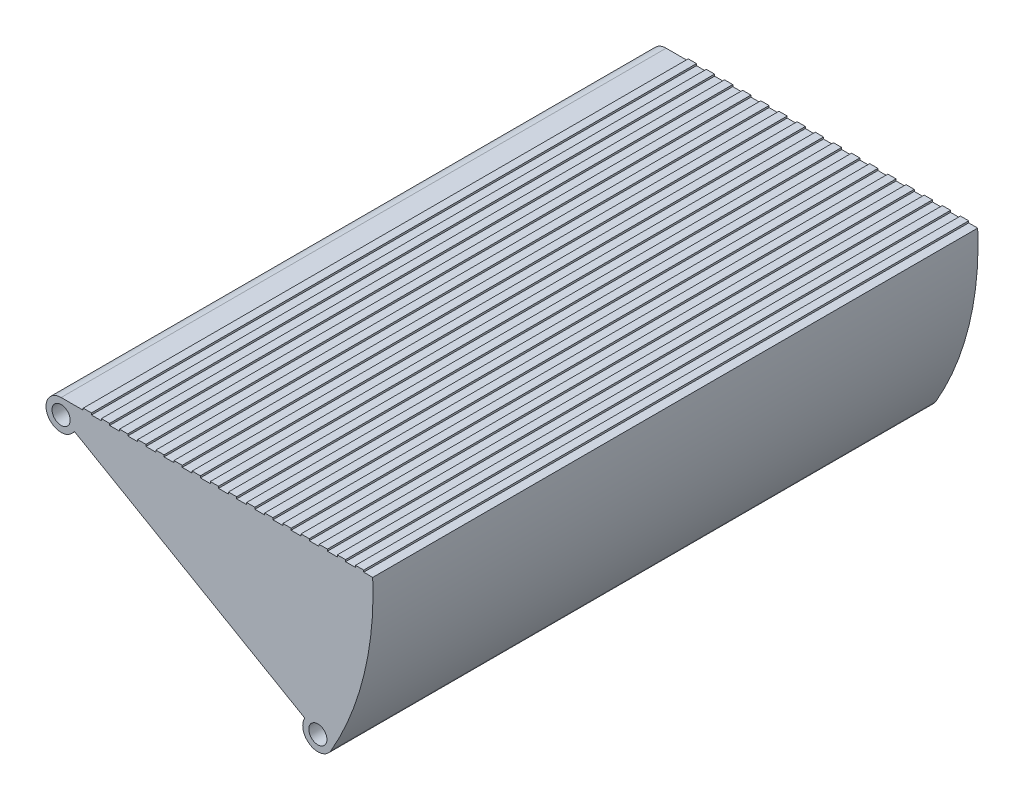
SolidWorks part; units mm, degrees
ref_plane "Front" through (0, 0, 0) normal (0, 0, 1) x (1, 0, 0)
ref_plane "Top" through (0, 0, 0) normal (0, 1, 0) x (1, 0, 0)
ref_plane "Right" through (0, 0, 0) normal (1, 0, 0) x (0, 0, -1)
sketch "Sketch1" plane through (0, 0, 0) normal (0, 0, 1) x (1, 0, 0)
  line L0 (90.6476, 270) -> (-424.3524, 270)
  line L1 (-402.7018, 232.5) -> (-21.6506, 12.5)
  circle A0 centre (-424.3524, 245) radius 15
  arc A1 (-21.6506, 12.5) -> (21.6506, -12.5) centre (0, 0) ccw
  arc A2 (21.6506, -12.5) -> (90.6476, 270) centre (-427.6732, 246.9173) ccw
  arc A3 (-424.3524, 270) -> (-402.7018, 232.5) centre (-424.3524, 245) ccw
  circle A4 centre (0, 0) radius 15
extrude "Boss-Extrude1" add sketch "Sketch1" along normal blind 1000
sketch "Sketch2" plane through (0, 0, 1000) normal (0, 0, 1) x (1, 0, 0)
  line L0 (90.6476, 270) -> (-424.3524, 270) construction
  line L1 (-387.8242, 270) -> (-374.2178, 270)
  line L2 (-387.8242, 270) -> (-387.8242, 273.0178)
  line L3 (-387.8242, 273.0178) -> (-374.2178, 273.0178)
  line L4 (-374.2178, 270) -> (-374.2178, 273.0178)
  line L5 (-357.8242, 270) -> (-357.8242, 273.0178)
  line L6 (-357.8242, 270) -> (-344.2178, 270)
  line L7 (-344.2178, 270) -> (-344.2178, 273.0178)
  line L8 (-357.8242, 273.0178) -> (-344.2178, 273.0178)
  line L9 (-327.8242, 270) -> (-327.8242, 273.0178)
  line L10 (-327.8242, 270) -> (-314.2178, 270)
  line L11 (-314.2178, 270) -> (-314.2178, 273.0178)
  line L12 (-327.8242, 273.0178) -> (-314.2178, 273.0178)
  line L13 (-297.8242, 270) -> (-297.8242, 273.0178)
  line L14 (-297.8242, 270) -> (-284.2178, 270)
  line L15 (-284.2178, 270) -> (-284.2178, 273.0178)
  line L16 (-297.8242, 273.0178) -> (-284.2178, 273.0178)
  line L17 (-267.8242, 270) -> (-267.8242, 273.0178)
  line L18 (-267.8242, 270) -> (-254.2178, 270)
  line L19 (-254.2178, 270) -> (-254.2178, 273.0178)
  line L20 (-267.8242, 273.0178) -> (-254.2178, 273.0178)
  line L21 (-237.8242, 270) -> (-237.8242, 273.0178)
  line L22 (-237.8242, 270) -> (-224.2178, 270)
  line L23 (-224.2178, 270) -> (-224.2178, 273.0178)
  line L24 (-237.8242, 273.0178) -> (-224.2178, 273.0178)
  line L25 (-207.8242, 270) -> (-207.8242, 273.0178)
  line L26 (-207.8242, 270) -> (-194.2178, 270)
  line L27 (-194.2178, 270) -> (-194.2178, 273.0178)
  line L28 (-207.8242, 273.0178) -> (-194.2178, 273.0178)
  line L29 (-177.8242, 270) -> (-177.8242, 273.0178)
  line L30 (-177.8242, 270) -> (-164.2178, 270)
  line L31 (-164.2178, 270) -> (-164.2178, 273.0178)
  line L32 (-177.8242, 273.0178) -> (-164.2178, 273.0178)
  line L33 (-147.8242, 270) -> (-147.8242, 273.0178)
  line L34 (-147.8242, 270) -> (-134.2178, 270)
  line L35 (-134.2178, 270) -> (-134.2178, 273.0178)
  line L36 (-147.8242, 273.0178) -> (-134.2178, 273.0178)
  line L37 (-117.8242, 270) -> (-117.8242, 273.0178)
  line L38 (-117.8242, 270) -> (-104.2178, 270)
  line L39 (-104.2178, 270) -> (-104.2178, 273.0178)
  line L40 (-117.8242, 273.0178) -> (-104.2178, 273.0178)
  line L41 (-87.8242, 270) -> (-87.8242, 273.0178)
  line L42 (-87.8242, 270) -> (-74.2178, 270)
  line L43 (-74.2178, 270) -> (-74.2178, 273.0178)
  line L44 (-87.8242, 273.0178) -> (-74.2178, 273.0178)
  line L45 (-57.8242, 270) -> (-57.8242, 273.0178)
  line L46 (-57.8242, 270) -> (-44.2178, 270)
  line L47 (-44.2178, 270) -> (-44.2178, 273.0178)
  line L48 (-57.8242, 273.0178) -> (-44.2178, 273.0178)
  line L49 (-27.8242, 270) -> (-27.8242, 273.0178)
  line L50 (-27.8242, 270) -> (-14.2178, 270)
  line L51 (-14.2178, 270) -> (-14.2178, 273.0178)
  line L52 (-27.8242, 273.0178) -> (-14.2178, 273.0178)
  line L53 (2.1758, 270) -> (2.1758, 273.0178)
  line L54 (2.1758, 270) -> (15.7822, 270)
  line L55 (15.7822, 270) -> (15.7822, 273.0178)
  line L56 (2.1758, 273.0178) -> (15.7822, 273.0178)
  line L57 (32.1758, 270) -> (32.1758, 273.0178)
  line L58 (32.1758, 270) -> (45.7822, 270)
  line L59 (45.7822, 270) -> (45.7822, 273.0178)
  line L60 (32.1758, 273.0178) -> (45.7822, 273.0178)
  line L61 (62.1758, 270) -> (62.1758, 273.0178)
  line L62 (62.1758, 270) -> (75.7822, 270)
  line L63 (75.7822, 270) -> (75.7822, 273.0178)
  line L64 (62.1758, 273.0178) -> (75.7822, 273.0178)
  dimension "D1" = 16
extrude "Boss-Extrude2" add sketch "Sketch2" against normal up to surface (1000 mm away) up to face at (-152.2371, 145.4333, 0)
shell "Shell1" thickness 20 removed face at (-212.1762, 122.5, 500)
